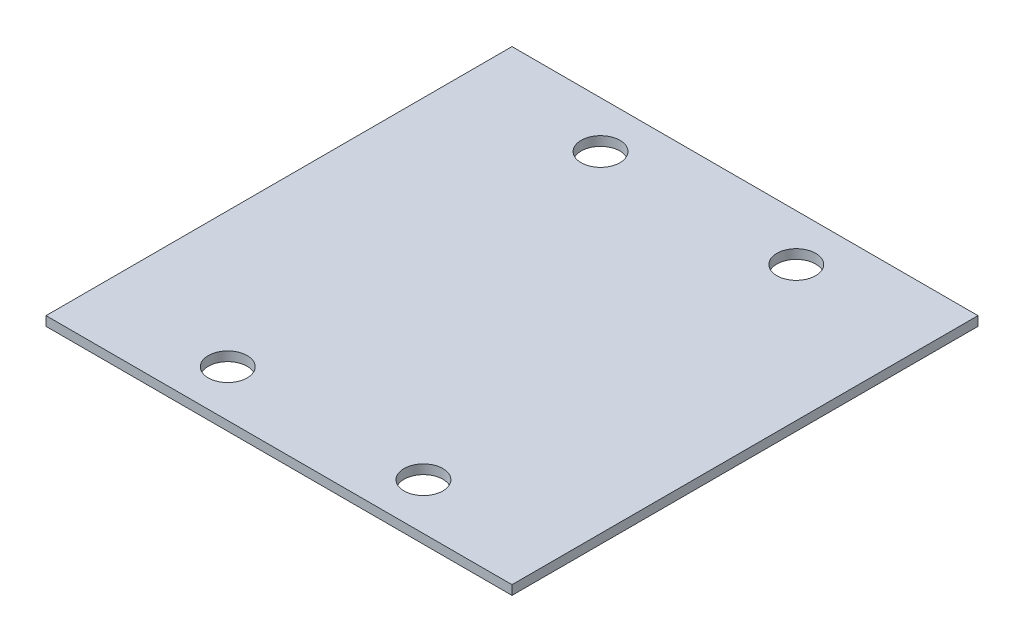
SolidWorks part; units mm, degrees
material "Plain Carbon Steel"
ref_plane "Front Plane" through (0, 0, 0) normal (0, 0, 1) x (1, 0, 0)
ref_plane "Top Plane" through (0, 0, 0) normal (0, 1, 0) x (1, 0, 0)
ref_plane "Right Plane" through (0, 0, 0) normal (1, 0, 0) x (0, 0, -1)
sketch "Sketch1" plane through (0, 0, 0) normal (0, 1, 0) x (1, 0, 0)
  line L1 (-38.1, -38.1) -> (38.1, -38.1)
  line L2 (-38.1, -38.1) -> (-38.1, 38.1)
  line L3 (-38.1, 38.1) -> (38.1, 38.1)
  line L4 (38.1, -38.1) -> (38.1, 38.1)
  line L5 (-38.1, -38.1) -> (38.1, 38.1) construction
  line L6 (-38.1, 38.1) -> (38.1, -38.1) construction
  point P0 (0, 0)
  point P6 (0, 38.1)
  dimension "D1" = 76.2
  dimension "D2" = 76.2
extrude "Boss-Extrude1" add sketch "Sketch1" along normal blind 1.524
sketch "Sketch3" plane through (0, 0, 0) normal (0, 1, 0) x (1, 0, 0)
  line L0 (0, 0) -> (0, 9.3414) construction
  line L1 (0, 9.3414) -> (0, 0) construction
  line L2 (0, 0) -> (-6.602, 0) construction
  line L3 (38.1, 38.1) -> (-38.1, 38.1) construction
  line L4 (-38.1, 38.1) -> (-38.1, -38.1) construction
  circle A0 centre (-16.002, 30.48) radius 3.175
  circle A1 centre (-16.002, -30.48) radius 3.175
  circle A2 centre (16.002, -30.48) radius 3.175
  circle A3 centre (16.002, 30.48) radius 3.175
  dimension "D1" = 6.35
  dimension "D2" = 7.62
  dimension "D3" = 22.098
extrude "Cut-Extrude3" cut sketch "Sketch3" along normal through all
sketch "Sketch4" plane through (0, 1.524, 0) normal (0, 1, 0) x (1, 0, 0)
  line L0 (38.1, 0) -> (-38.1, 0) construction
  line L1 (38.1, -38.1) -> (38.1, 38.1) construction
  line L2 (-38.1, 38.1) -> (-38.1, -38.1) construction
  line L3 (0, -38.1) -> (0, 38.1) construction
  line L4 (-38.1, -38.1) -> (38.1, -38.1) construction
  line L5 (38.1, 38.1) -> (-38.1, 38.1) construction
sketch "Sketch8" plane through (0, 0, 0) normal (0, -1, 0) x (1, 0, 0)
  line L4 (38.1, 0) -> (-38.1, 0) construction
  line L5 (0, 38.1) -> (0, -38.1) construction
  line L6 (38.1, 0) -> (-38.1, 0) construction
  line L7 (0, 38.1) -> (0, -38.1) construction
  circle A0 centre (0, 0) radius 11.684 construction
  point P4 (0, 0)
